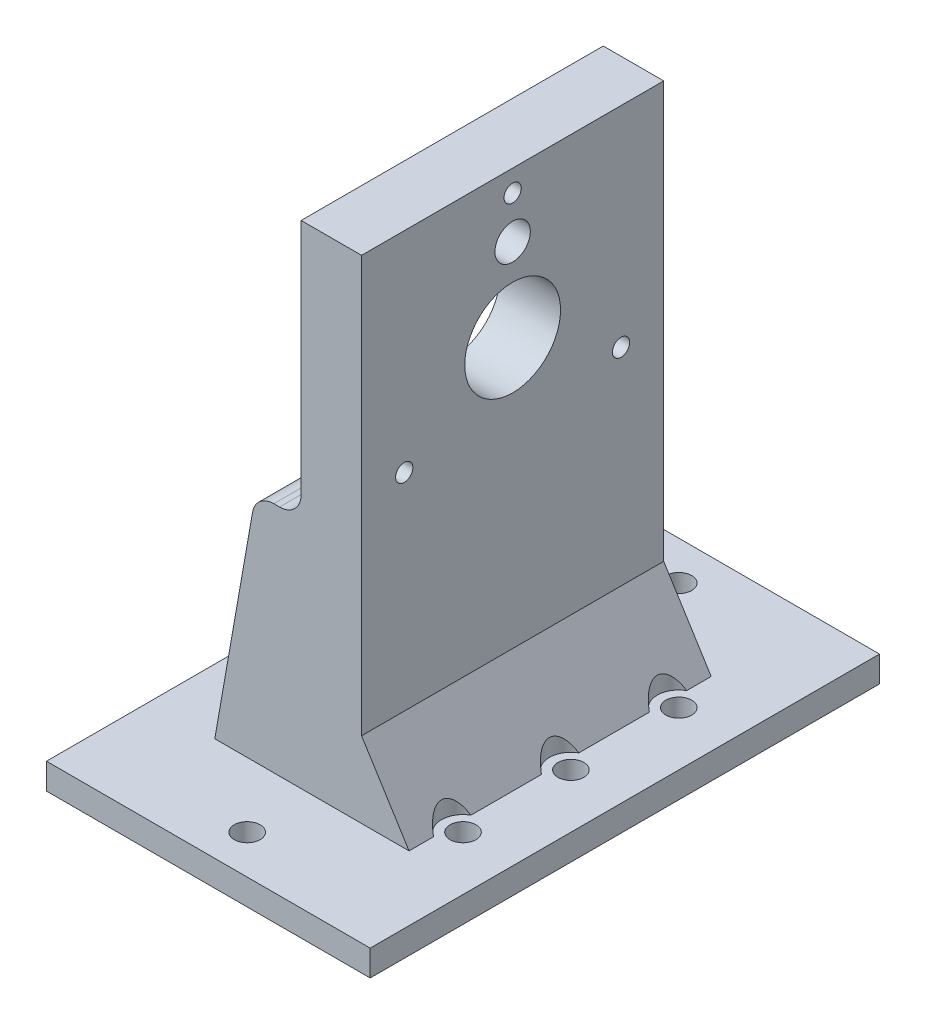
SolidWorks part; units mm, degrees
ref_plane "前视基准面" through (0, 0, 0) normal (0, 0, 1) x (1, 0, 0)
ref_plane "上视基准面" through (0, 0, 0) normal (0, 1, 0) x (1, 0, 0)
ref_plane "右视基准面" through (0, 0, 0) normal (1, 0, 0) x (0, 0, -1)
sketch "草图1" plane through (0, 0, 0) normal (0, 1, 0) x (1, 0, 0)
  line L0 (0, 0) -> (35, 0)
  line L1 (35, 0) -> (35, -70)
  line L2 (35, -70) -> (0, -70)
  line L3 (0, -70) -> (0, 0)
  line L4 (35, 0) -> (40, 0)
  line L5 (40, 0) -> (40, -70)
  line L6 (40, -70) -> (35, -70)
  line L7 (37.5, -70) -> (37.5, 0) construction
  line L8 (40, -70) -> (75, -70)
  line L9 (40, 0) -> (40, -70)
  line L10 (75, -70) -> (75, 0)
  line L11 (75, 0) -> (40, 0)
  line L12 (40, 0) -> (49, 0)
  line L13 (49, 0) -> (49, -70)
extrude "凸台-拉伸1" add sketch "草图1" along normal blind 6 contours L3 L2 L1 L0 | L10 L11 L5 L8 region at (17.5, 0, 35) region at (62, 0, 35)
extrude "凸台-拉伸2" add sketch "草图1<3>" along normal blind 120 contours L7 L6 L5 L4 | L6 L7 L4 L1 | L13 L11 L5 L8 region at (36.25, 0, 35) region at (38.75, 0, 35) region at (44.5, 0, 35)
sketch "草图1<3>" plane through (0, 0, 0) normal (0, 1, 0) x (1, 0, 0) same geometry as "草图1"
sketch "草图3" plane through (35, 0, 0) normal (-1, 0, 0) x (0, 0, 1)
  line L0 (35, 86) -> (35, 105.25)
  line L2 (0, 6) -> (70, 6) construction
  line L3 (35, 6) -> (35, 86)
  line L4 (35, 105.25) -> (35, 115)
  circle A0 centre (35, 86) radius 11.1
  circle A1 centre (35, 105.25) radius 4.1
  circle A2 centre (35, 86) radius 29
  circle A3 centre (35, 115) radius 2
  circle A8 centre (60.1147, 71.5) radius 2
  circle A9 centre (9.8853, 71.5) radius 2
  point P16 (35, 103)
  point P17 (35, 86)
  point P18 (35, 73)
  dimension "D1" = 3
sketch "草图4" plane through (0, 0, 0) normal (0, 0, -1) x (-1, 0, 0)
  line L0 (-40, 6) -> (-60, 6)
  line L1 (-75, 6) -> (-49, 6) construction
  line L2 (-60, 6) -> (-40, 38)
  line L4 (-40, 38) -> (-40, 6)
  line L5 (-37.5, 0) -> (-37.5, 35.1786) construction
  line L6 (-35, 0) -> (-40, 0) construction
  line L7 (-15, 6) -> (-35, 38)
  line L8 (-35, 6) -> (-15, 6)
  line L9 (-35, 38) -> (-35, 6)
  line M7 (0, 6) -> (-35, 6)
  line M8 (-35, 6) -> (-35, 120)
extrude "凸台-拉伸4" add sketch "草图4" against normal through all contours L7 M7 M8 | L2 L4 L0 region at (28.3333, 16.6667, 0)
sketch "草图5" plane through (35, 0, 0) normal (-1, 0, 0) x (0, 0, 1)
  line L0 (0, 120) -> (0, 125)
  line L1 (0, 120) -> (0, 38) construction
  line L2 (0, 125) -> (23.3812, 137.5)
  line L3 (35, 120) -> (35, 38) construction
  line L4 (0, 120) -> (70, 120) construction
  line L5 (70, 38) -> (0, 38) construction
  line L6 (23.3812, 137.5) -> (46.6188, 137.5)
  line L7 (0, 120) -> (70, 120)
  line L8 (70, 120) -> (70, 125)
  line L9 (70, 125) -> (46.6188, 137.5)
  point P16 (35, 137.5)
sketch "草图9" plane through (0, 0, 0) normal (0, 0, -1) x (-1, 0, 0)
  line L0 (-35, 120) -> (-15, 6)
  line L1 (-35, 120) -> (-35, 125) construction
  line L2 (-35, 120) -> (-49, 120) construction
  line L5 (-35, 120) -> (-35, 0)
  line L6 (-35, 0) -> (0, 0) construction
  line L7 (-40, 0) -> (-35, 0) construction
  line L8 (-35, 0) -> (-15, 6)
extrude "凸台-拉伸7" add sketch "草图9" against normal through all contours L0 L8 L5
sketch "草图7" plane through (0, 0, 0) normal (0, -1, 0) x (1, 0, 0)
  line L0 (12.5, 70) -> (62.5, 70)
  line L2 (40, 70) -> (75, 70) construction
  line L3 (62.5, 70) -> (62.5, 0)
  line L4 (75, 0) -> (40, 0) construction
  circle A0 centre (62.5, 35) radius 3
  circle A1 centre (12.5, 35) radius 3
  circle A2 centre (12.5, 60) radius 3
  circle A3 centre (62.5, 60) radius 3
  circle A4 centre (62.5, 10) radius 3
  circle A5 centre (12.5, 10) radius 3
  point P3 (37.5, 70)
  dimension "D1" = 2
  dimension "D2" = 2
  dimension "D3" = 2
extrude "切除-拉伸4" cut sketch "草图7" against normal through all contours A1 | A2 | A5 | L3 A4 | L3 A4 | L3 A0 | L3 A0 | L3 A3 | L3 A3 region at (63.7732, 0, 60) region at (63.7732, 0, 10) region at (61.2268, 0, 10) region at (63.7732, 0, 35) region at (61.2268, 0, 35) region at (61.2268, 0, 60) region at (12.5, 0, 35) region at (12.5, 0, 60) region at (12.5, 0, 10)
sketch "草图8" plane through (0, 6, 0) normal (0, 1, 0) x (1, 0, 0)
  circle A0 centre (12.5, -10) radius 5
  circle A1 centre (62.5, -10) radius 5
  circle A2 centre (62.5, -35) radius 5
  circle A3 centre (62.5, -60) radius 5
  circle A4 centre (12.5, -35) radius 5
  circle A5 centre (12.5, -60) radius 5
  dimension "D1" = 2
  dimension "D2" = 3
extrude "切除-拉伸5" cut sketch "草图8" along normal blind 115
extrude "切除-拉伸8" cut sketch "草图3" against normal through all both and the other way through all contours A3 | A0 | A8 | A9 | A1
sketch "草图10" plane through (0, 0, 0) normal (0, -1, 0) x (1, 0, 0)
  line L0 (0, 70) -> (0, 94)
  line L1 (0, 94) -> (75, 94)
  line L2 (75, 94) -> (75, 70)
  line L3 (75, 70) -> (0, 70)
extrude "凸台-拉伸8" add sketch "草图10" against normal blind 6 contours L0 L1 L2 L3
sketch "草图11" plane through (0, 6, 0) normal (0, 1, 0) x (1, 0, 0)
  line L0 (12.5, -60) -> (37.5, -60)
  line L1 (37.5, -70) -> (37.5, 0) construction
  line L2 (37.5, -60) -> (37.5, -85)
  circle A0 centre (37.5, -85) radius 3
extrude "切除-拉伸9" cut sketch "草图11" against normal blind 6 contours A0
ref_plane "基准面1" through (0, 0, 35) normal (0, 0, 1) x (1, 0, 0)
mirror "镜向1" about plane through (0, 0, 35) normal (0, 0, 1) of "凸台-拉伸8", "切除-拉伸9"
sketch "草图12" plane through (0, 120, 0) normal (0, 1, 0) x (1, 0, 0)
  line L0 (35, 0) -> (35, -70)
  line L4 (35, -70) -> (-21.4659, -70)
  line L5 (-21.4659, -70) -> (-21.4659, 0)
  line L6 (-21.4659, 0) -> (35, 0)
extrude "切除-拉伸10" cut sketch "草图12" against normal blind 60 contours L5 L6 L0 L4
fillet "圆角1" radius 5 2 edges at (24.4737, 60, 35) (35, 60, 35)
